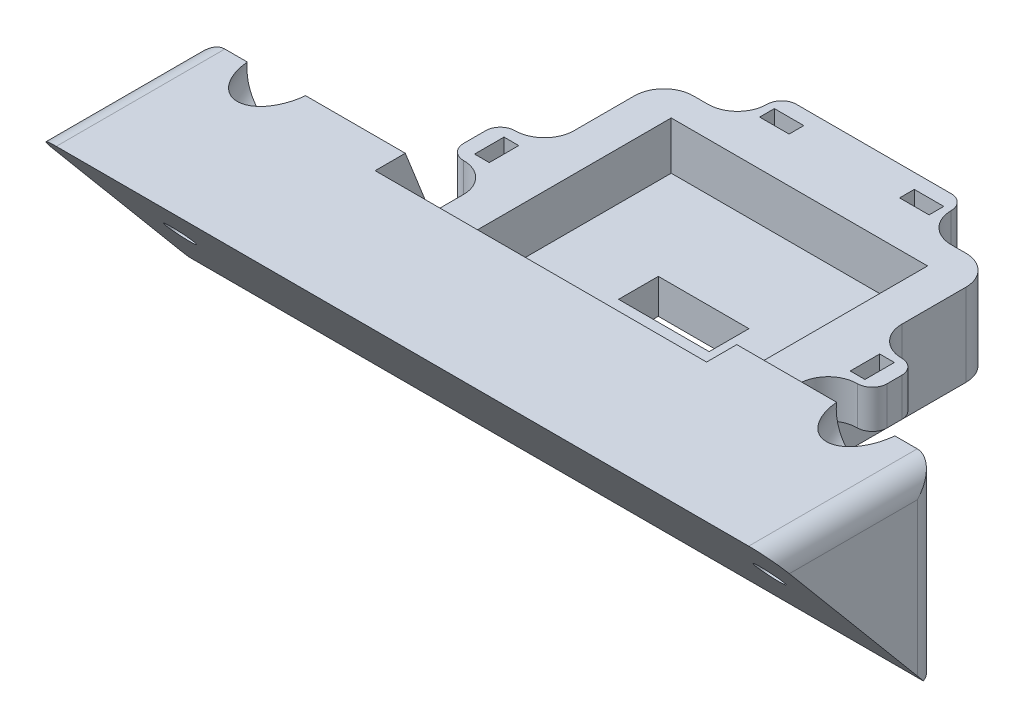
SolidWorks part; units mm, degrees
ref_plane "Front Plane" through (0, 0, 0) normal (0, 0, 1) x (1, 0, 0)
ref_plane "Top Plane" through (0, 0, 0) normal (0, 1, 0) x (1, 0, 0)
ref_plane "Right Plane" through (0, 0, 0) normal (1, 0, 0) x (0, 0, -1)
sketch "Sketch2" plane through (0, 0, 0) normal (0, 1, 0) x (1, 0, 0)
  line L1 (0, 0) -> (57.15, 0)
  line L2 (0, 0) -> (0, 49.784)
  line L3 (0, 49.784) -> (57.15, 49.784)
  line L4 (57.15, 0) -> (57.15, 49.784)
  dimension "D1" = 57.15
  dimension "D2" = 49.784
extrude "Boss-Extrude1" add sketch "Sketch2" along normal blind 14.224
sketch "Sketch3" plane through (0, 14.224, 0) normal (0, 1, 0) x (1, 0, 0)
  line L0 (0, 49.784) -> (0, 0) construction
  line L1 (6.477, 44.577) -> (50.673, 44.577)
  line L2 (6.477, 44.577) -> (6.477, 5.207)
  line L3 (6.477, 5.207) -> (50.673, 5.207)
  line L4 (50.673, 44.577) -> (50.673, 5.207)
  line L5 (57.15, 49.784) -> (0, 49.784) construction
  point P6 (0, 24.892)
  point P7 (6.477, 24.892)
  point P10 (28.575, 49.784)
  point P11 (28.575, 44.577)
  dimension "D1" = 44.196
  dimension "D2" = 39.37
extrude "Cut-Extrude1" cut sketch "Sketch3" against normal blind 8.255
sketch "Sketch4" plane through (0, 5.969, 0) normal (0, 1, 0) x (1, 0, 0)
  line L1 (10.795, 14.605) -> (46.355, 14.605)
  line L2 (10.795, 14.605) -> (10.795, 10.414)
  line L3 (10.795, 10.414) -> (46.355, 10.414)
  line L4 (46.355, 14.605) -> (46.355, 10.414)
  line L6 (6.477, 5.207) -> (50.673, 5.207) construction
  line L7 (50.673, 44.577) -> (6.477, 44.577) construction
  line L8 (20.7645, 28.067) -> (36.3855, 28.067)
  line L9 (20.7645, 28.067) -> (20.7645, 21.209)
  line L10 (20.7645, 21.209) -> (36.3855, 21.209)
  line L11 (36.3855, 28.067) -> (36.3855, 21.209)
  line L12 (6.477, 5.207) -> (50.673, 5.207) construction
  point P6 (28.575, 5.207)
  point P7 (28.575, 10.414)
  point P10 (28.575, 21.209)
  point P15 (28.575, 14.605)
  dimension "D1" = 35.56
  dimension "D3" = 9.398
  dimension "D4" = 4.191
  dimension "D5" = 15.621
  dimension "D6" = 6.858
  dimension "D7" = 16.51
extrude "Cut-Extrude2" cut sketch "Sketch4" against normal blind 8.255
sketch "Sketch5" plane through (0, 14.224, 0) normal (0, 1, 0) x (1, 0, 0)
  line L0 (0, 49.784) -> (0, 0) construction
  line L5 (57.15, 49.784) -> (0, 49.784) construction
  line L6 (0, 29.21) -> (-7.62, 29.21)
  line L7 (0, 29.21) -> (0, 20.32)
  line L8 (0, 20.32) -> (-7.62, 20.32)
  line L9 (-7.62, 29.21) -> (-7.62, 20.32)
  line L10 (12.7, 49.784) -> (36.83, 49.784)
  line L11 (12.7, 49.784) -> (12.7, 57.404)
  line L12 (12.7, 57.404) -> (36.83, 57.404)
  line L15 (36.83, 49.784) -> (44.45, 49.784)
  line L17 (36.83, 57.404) -> (44.45, 57.404)
  line L18 (44.45, 49.784) -> (44.45, 57.404)
  line L23 (57.15, 0) -> (57.15, 49.784) construction
  line L24 (57.15, 28.575) -> (64.77, 28.575)
  line L25 (57.15, 28.575) -> (57.15, 20.955)
  line L26 (57.15, 20.955) -> (64.77, 20.955)
  line L27 (64.77, 28.575) -> (64.77, 20.955)
  line L29 (0, 0) -> (57.15, 0) construction
  point P1 (0, 24.765)
  point P2 (57.15, 24.765)
  dimension "D1" = 8.89
  dimension "D2" = 7.62
  dimension "D3" = 29.21
  dimension "D4" = 12.7
  dimension "D5" = 12.7
extrude "Boss-Extrude2" add sketch "Sketch5" against normal blind 6.604
sketch "Sketch6" plane through (0, 14.224, 0) normal (0, 1, 0) x (1, 0, 0)
  line L1 (-5.08, 27.305) -> (-2.54, 27.305)
  line L2 (-5.08, 27.305) -> (-5.08, 22.225)
  line L3 (-5.08, 22.225) -> (-2.54, 22.225)
  line L4 (-2.54, 27.305) -> (-2.54, 22.225)
  line L13 (59.69, 27.305) -> (62.23, 27.305)
  line L14 (59.69, 27.305) -> (59.69, 22.225)
  line L15 (59.69, 22.225) -> (62.23, 22.225)
  line L16 (62.23, 27.305) -> (62.23, 22.225)
  line L18 (-7.62, 29.21) -> (-7.62, 20.32) construction
  line L19 (64.77, 20.955) -> (64.77, 28.575) construction
  line L20 (44.45, 57.404) -> (12.7, 57.404) construction
  line L22 (13.97, 54.864) -> (19.05, 54.864)
  line L23 (13.97, 54.864) -> (13.97, 52.324)
  line L24 (13.97, 52.324) -> (19.05, 52.324)
  line L25 (19.05, 54.864) -> (19.05, 52.324)
  line L26 (0, 49.784) -> (0, 29.21) construction
  line L30 (57.15, 28.575) -> (57.15, 49.784) construction
  line L31 (38.1, 54.864) -> (43.18, 54.864)
  line L32 (38.1, 54.864) -> (38.1, 52.324)
  line L33 (38.1, 52.324) -> (43.18, 52.324)
  line L34 (43.18, 54.864) -> (43.18, 52.324)
  point P28 (-7.62, 24.765)
  point P29 (-5.08, 24.765)
  point P30 (-2.54, 24.765)
  point P31 (59.69, 24.765)
  dimension "D1" = 5.08
  dimension "D2" = 2.54
  dimension "D3" = 5.08
  dimension "D4" = 2.54
  dimension "D5" = 5.08
  dimension "D6" = 2.54
  dimension "D7" = 2.54
  dimension "D8" = 2.54
  dimension "D9" = 2.54
  dimension "D10" = 2.54
  dimension "D11" = 2.54
  dimension "D12" = 5.08
  dimension "D13" = 13.97
  dimension "D14" = 13.97
extrude "Cut-Extrude3" cut sketch "Sketch6" against normal blind 6.604
fillet "Fillet1" radius 5.08 4 edges at (0, 7.112, -49.784) (0, 7.112, 0) (57.15, 7.112, 0) (57.15, 7.112, -49.784)
fillet "Fillet2" radius 2.54 6 edges at (64.77, 10.922, -20.955) (64.77, 10.922, -28.575) (-7.62, 10.922, -20.32) (-7.62, 10.922, -29.21) (44.45, 10.922, -57.404) (12.7, 10.922, -57.404)
sketch "Sketch7" plane through (0, 0, 0) normal (0, 0, 1) x (1, 0, 0)
  line L0 (-34.925, 14.224) -> (92.075, 14.224)
  line L1 (92.075, 14.224) -> (92.075, 0)
  line L2 (92.075, 0) -> (-34.925, 0)
  line L3 (-34.925, 0) -> (-34.925, 14.224)
  line L4 (5.08, 14.224) -> (52.07, 14.224) construction
  line L5 (5.08, 0) -> (52.07, 0) construction
  circle A0 centre (-30.861, 7.112) radius 2.3813
  circle A1 centre (88.011, 7.112) radius 2.3813
  point P9 (28.575, 0)
  point P10 (28.575, 0)
  point P18 (-34.925, 7.112)
  dimension "D1" = 4.7625
  dimension "D2" = 4.064
  dimension "D3" = 4.064
  dimension "D4" = 127
extrude "Boss-Extrude3" add sketch "Sketch7" against normal up to surface (5.207 mm away) up to face at (28.575, 10.0965, -5.207)
sketch "Sketch8" plane through (-34.925, 0, 0) normal (-1, 0, 0) x (0, 0, 1)
  line L1 (0, 25.4) -> (21.3131, 25.4)
  line L2 (21.3131, 25.4) -> (0, 0)
  line L3 (0, 0) -> (-5.207, 0)
  line L5 (0, 25.4) -> (0, 14.224)
  line L6 (0, 14.224) -> (0, 0) construction
  line L7 (0, 14.224) -> (-5.207, 14.224)
  line L8 (-5.207, 14.224) -> (-5.207, 0)
  dimension "D1" = 50
  dimension "D2" = 25.4
extrude "Boss-Extrude4" add sketch "Sketch8" against normal up to surface (127 mm away) up to face at (92.075, 7.112, -2.6035)
sketch "Sketch11" plane through (0, 0, 0) normal (0, 0, -1) x (-1, 0, 0)
  line L0 (34.925, 14.224) -> (-92.075, 14.224) construction
  line L1 (34.925, 25.4) -> (0, 25.4)
  line L2 (34.925, 25.4) -> (34.925, 14.224)
  line L3 (34.925, 14.224) -> (0, 14.224)
  line L4 (0, 25.4) -> (0, 14.224)
  line L6 (-92.075, 25.4) -> (-57.15, 25.4)
  line L7 (-92.075, 25.4) -> (-92.075, 14.224)
  line L8 (-92.075, 14.224) -> (-57.15, 14.224)
  line L9 (-57.15, 25.4) -> (-57.15, 14.224)
extrude "Boss-Extrude5" add sketch "Sketch11" along normal up to surface (5.207 mm away) up to face at (74.6125, 7.112, -5.207)
sketch "Sketch9" plane through (0, 0, 0) normal (0, -0.6428, 0.766) x (1, 0, 0)
  line L2 (92.075, 33.1573) -> (-34.925, 33.1573) construction
  line L3 (-22.225, 15.3773) -> (79.375, 15.3773) construction
  line L4 (-34.925, 0) -> (92.075, 0) construction
  circle A0 centre (-22.225, 15.3773) radius 2.413
  circle A1 centre (79.375, 15.3773) radius 2.413
  point P6 (28.575, 0)
  point P7 (28.575, 15.3773)
  dimension "D1" = 4.826
  dimension "D2" = 101.6
  dimension "D4" = 17.78
extrude "Cut-Extrude4" cut sketch "Sketch9" against normal mid plane 50.8
fillet "Fillet3" radius 5.08 2 edges at (44.45, 10.922, -49.784) (12.7, 10.922, -49.784)
fillet "Fillet4" radius 5.08 4 edges at (57.15, 10.922, -20.955) (57.15, 10.922, -28.575) (0, 10.922, -29.21) (0, 10.922, -20.32)
sketch "Sketch12" plane through (0, 0, 0) normal (-1, 0, 0) x (0, 0, 1)
  line L0 (-5.207, 25.4) -> (-15.24, 0)
  line L1 (-44.704, 0) -> (-5.207, 0) construction
  line L2 (-15.24, 0) -> (-5.207, 0)
  line L3 (-5.207, 0) -> (-5.207, 25.4)
extrude "Boss-Extrude6" add sketch "Sketch12" along normal blind 6.35
sketch "Sketch13" plane through (57.15, 0, 0) normal (1, 0, 0) x (0, 0, -1)
  line L0 (5.207, 25.4) -> (15.875, 0)
  line L1 (5.207, 0) -> (44.704, 0) construction
  line L2 (15.875, 0) -> (5.207, 0)
  line L3 (5.207, 0) -> (5.207, 25.4)
extrude "Boss-Extrude7" add sketch "Sketch13" along normal blind 6.35
sketch "Sketch14" plane through (-34.925, 0, 0) normal (-1, 0, 0) x (0, 0, 1)
  line L0 (-5.207, 0) -> (-5.207, -6.2055)
  line L1 (-5.207, -6.2055) -> (0, 0)
  line L2 (0, 0) -> (-5.207, 0)
  line L3 (0, 0) -> (21.3131, 25.4) construction
extrude "Boss-Extrude8" add sketch "Sketch14" against normal up to surface (127 mm away) up to face at (92.075, 12.7, 2.7248)
sketch "Sketch15" plane through (92.075, 0, 0) normal (1, 0, 0) x (0, 0, -1)
  line L0 (5.207, -6.2055) -> (2.667, -6.2055)
  line L1 (2.667, -6.2055) -> (-23.8531, 25.4)
  line L2 (-23.8531, 25.4) -> (-21.3131, 25.4)
  line L3 (-21.3131, 25.4) -> (5.207, -6.2055)
  dimension "D1" = 2.54
extrude "Boss-Extrude9" add sketch "Sketch15" against normal up to surface (127 mm away) up to face at (-34.925, 14.8648, 3.633)
sketch "Sketch16" plane through (0, 0, 0) normal (0, 0.6428, -0.766) x (-1, 0, 0)
  circle A0 centre (-79.375, 15.3773) radius 2.413
  circle A1 centre (22.225, 15.3773) radius 2.413
  circle A2 centre (-79.375, 15.3773) radius 2.413 construction
  circle A3 centre (22.225, 15.3773) radius 2.413 construction
extrude "Cut-Extrude6" cut sketch "Sketch16" against normal up to surface (1.9458 mm away) up to face at (28.575, 9.5973, 10.5931)
sketch "Sketch17" plane through (0, -1.2507, 1.4905) normal (0, -0.6428, 0.766) x (1, 0, 0)
  circle A0 centre (79.375, 15.3773) radius 5.08
  circle A1 centre (-22.225, 15.3773) radius 5.08
  dimension "D1" = 10.16
  dimension "D2" = 10.16
extrude "Cut-Extrude9" cut sketch "Sketch17" along normal offset from surface (17.78 mm away) 10.16 from offset 27.94 up to face at (79.375, 8.6806, 9.8239) offset against normal yes
fillet "Fillet5" radius 3.81 4 edges at (92.075, 25.4, 9.3231) (92.075, 9.5973, -5.207) (-34.925, 25.4, 9.3231) (-34.925, 9.5973, -5.207)
